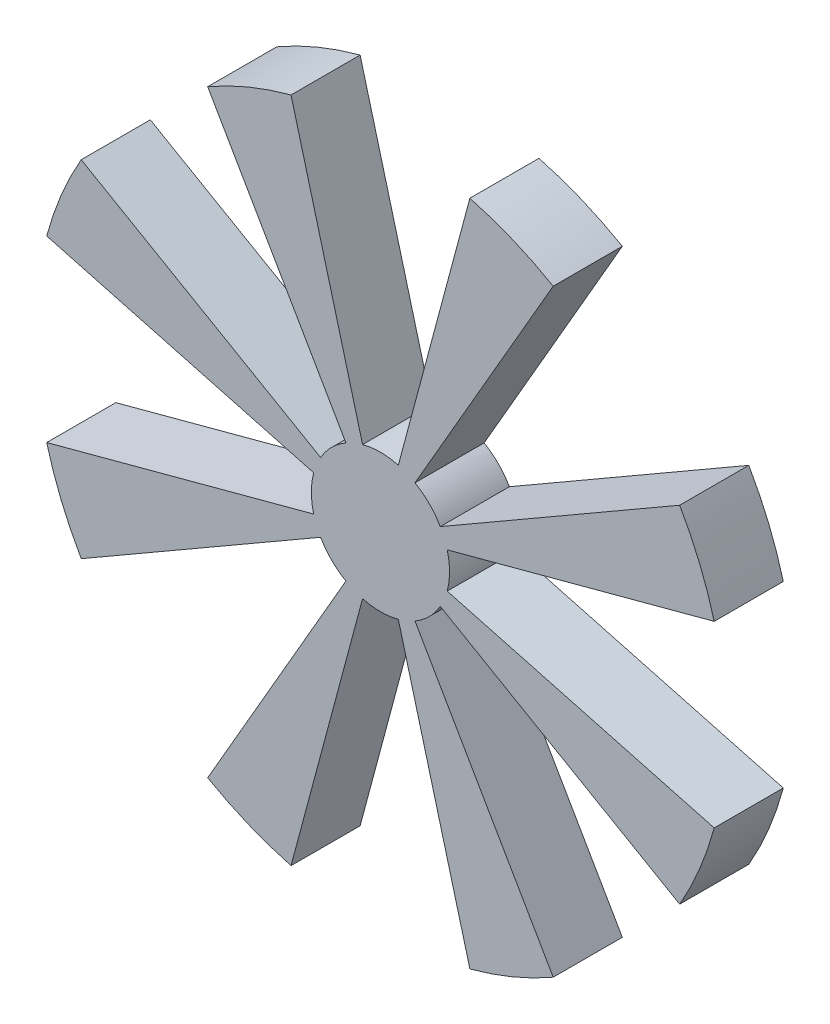
SolidWorks part; units mm, degrees
ref_plane "Plan de face" through (0, 0, 0) normal (0, 0, 1) x (1, 0, 0)
ref_plane "Plan de dessus" through (0, 0, 0) normal (0, 1, 0) x (1, 0, 0)
ref_plane "Plan de droite" through (0, 0, 0) normal (1, 0, 0) x (0, 0, -1)
sketch "Esquisse1" plane through (0, 0, 0) normal (0, 0, 1) x (1, 0, 0)
  line L0 (1.2941, 4.8296) -> (6.4705, 24.1481)
  line L1 (2.5, 4.3301) -> (12.5, 21.6506)
  line L2 (0, 0) -> (0, 28.1816) construction
  arc A0 (2.5, 4.3301) -> (1.2941, 4.8296) centre (0, 0) ccw
  arc A1 (12.5, 21.6506) -> (6.4705, 24.1481) centre (0, 0) ccw
  dimension "D1" = 10
  dimension "D2" = 50
  dimension "D3" = 15
  dimension "D4" = 15
extrude "Boss.-Extru.1" add sketch "Esquisse1" along normal blind 5 contours L0 A1 L1 A0
ref_axis "Axe1" through (0, 0, 28.2561) along (0, 0, -1)
pattern_circular "Répétition circulaire1" count 8 over 360 about axis through (0, 0, 28.2561) along (0, 0, -1) of bodies 101
sketch "Esquisse2" plane through (0, 0, 0) normal (0, 0, 1) x (1, 0, 0)
  circle A0 centre (0, 0) radius 5
  dimension "D1" = 10
extrude "Boss.-Extru.2" add sketch "Esquisse2" along normal blind 5
